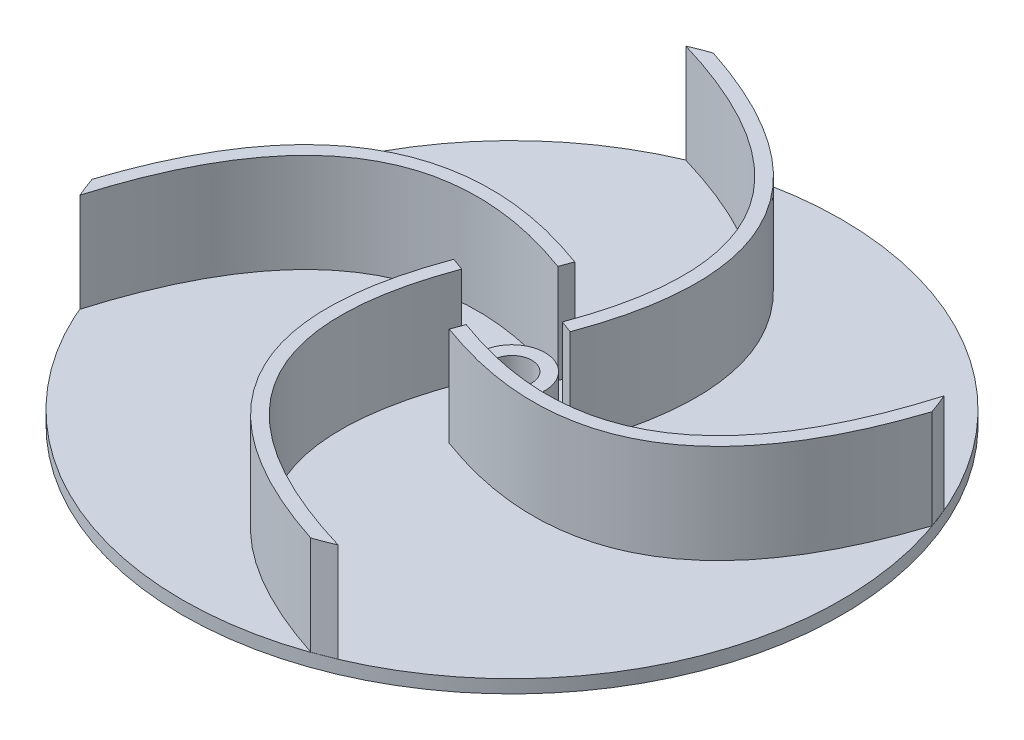
SolidWorks part; units mm, degrees
ref_plane "Front Plane" through (0, 0, 0) normal (0, 0, 1) x (1, 0, 0)
ref_plane "Top Plane" through (0, 0, 0) normal (0, 1, 0) x (1, 0, 0)
ref_plane "Right Plane" through (0, 0, 0) normal (1, 0, 0) x (0, 0, -1)
sketch "Sketch1" plane through (0, 0, 0) normal (0, 1, 0) x (1, 0, 0)
  circle A0 centre (0, 0) radius 50
  dimension "D1" = 100
extrude "Boss-Extrude1" add sketch "Sketch1" along normal blind 2
sketch "Sketch2" plane through (0, 0, 0) normal (0, 1, 0) x (1, 0, 0)
  circle A0 centre (0, 0) radius 5
  dimension "D1" = 10
extrude "Boss-Extrude2" add sketch "Sketch2" along normal blind 7
sketch "Sketch3" plane through (0, 2, 0) normal (0, 1, 0) x (1, 0, 0)
  line L0 (0.3472, 9.1743) -> (-0.3472, 7.2987)
  circle A2 centre (0, 0) radius 5
  circle A3 centre (0, 0) radius 5 construction
  arc A4 (-45.9621, -19.5836) -> (-47.1259, -16.5886) centre (0, 0) cw
  spline S0 degree 2 poles (0, 8.2365) (-41.2859, 23.5198) (-50.5083, -35.737) knots 0 0 0 1 1 1
  spline S1 degree 1 poles (0.3472, 9.1743) (-51.4964, -35.5832) knots 0 0 1 1 construction
  spline S2 degree 2 poles (0.3472, 9.1743) (-2.2723, 10.144) (-9.7785, 12.1762) (-18.8587, 12.5168) (-26.9833, 10.4378) (-35.8341, 4.8056) (-43.1924, -6.0589) (-47.1923, -16.4414) (-50.2499, -27.5746) (-51.4964, -35.5832) knots 0 0 0 0.0625 0.1875 0.3125 0.4375 0.625 0.776076 0.865646 1 1 1
  spline S3 degree 1 poles (-0.3472, 7.2987) (-49.5202, -35.8908) knots 0 0 1 1 construction
  spline S4 degree 2 poles (-0.3472, 7.2987) (-2.8884, 8.2394) (-10.113, 10.1914) (-18.6698, 10.5043) (-26.1782, 8.5781) (-34.3636, 3.3804) (-42.0583, -7.9307) (-46.0083, -19.4722) (-48.4634, -29.1084) (-49.5202, -35.8908) knots 0 0 0 0.0625 0.1875 0.3125 0.4375 0.625 0.808104 0.884862 1 1 1
  dimension "D3" = 10
  dimension "D1" = 1
  dimension "D2" = 1
sketch "Sketch4" plane through (0, 0, 0) normal (0, 1, 0) x (1, 0, 0)
  line L0 (-2.5981, -1.5) -> (2.5981, -1.5)
  arc A0 (2.5981, -1.5) -> (-2.5981, -1.5) centre (0, 0) ccw
  dimension "D1" = 6
  dimension "D2" = 1.5
extrude "Cut-Extrude2" cut sketch "Sketch4" along normal through all contours A0 L0
extrude "Boss-Extrude4" add sketch "Sketch3" along normal blind 15 contours S4 L0 S0 A4 | L0 S2 A4 S0 region at (-0.3555, 2, -8.9013) region at (-0.6979, 2, -7.9617)
pattern_circular "CirPattern1" count 4 over 360 about axis through (0, 7, 0) along (0, 1, 0) of "Boss-Extrude4"
